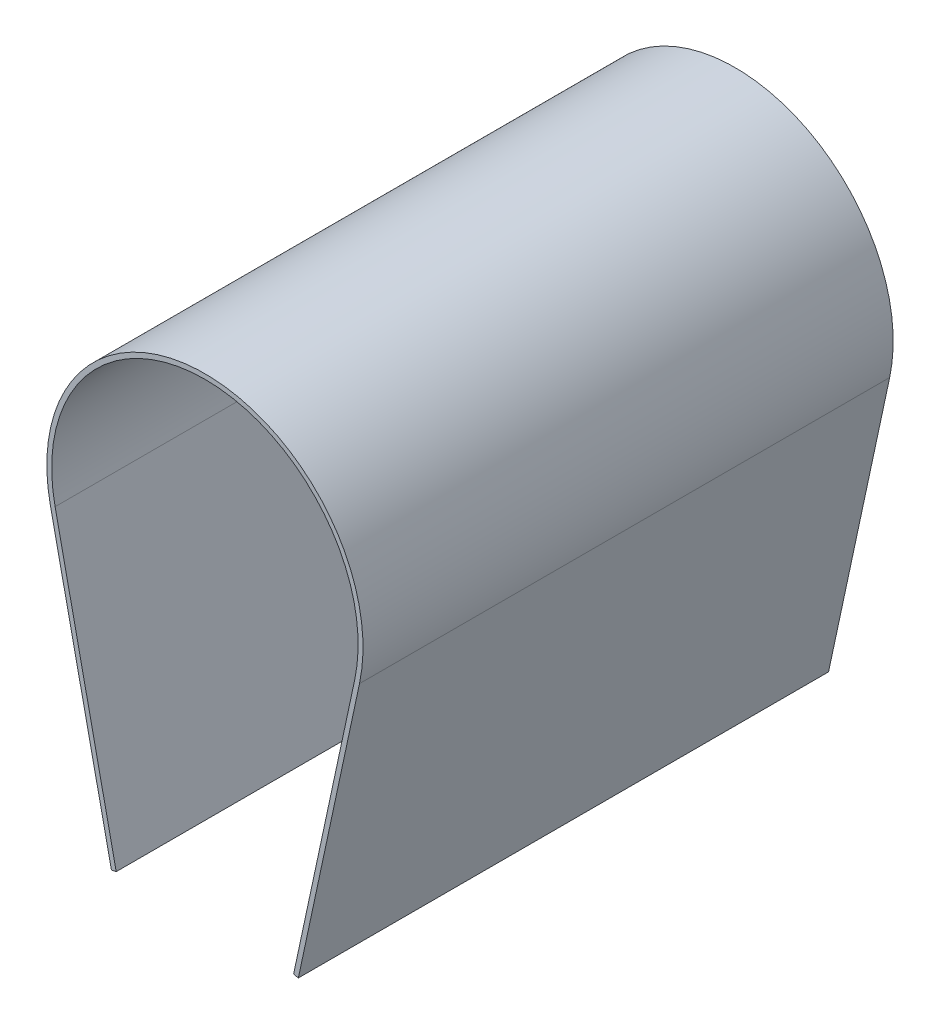
SolidWorks part; units mm, degrees
ref_plane "Front Plane" through (0, 0, 0) normal (0, 0, 1) x (1, 0, 0)
ref_plane "Top Plane" through (0, 0, 0) normal (0, 1, 0) x (1, 0, 0)
ref_plane "Right Plane" through (0, 0, 0) normal (1, 0, 0) x (0, 0, -1)
sketch "Cross Section Sketch" plane through (0, 0, 0) normal (0, 0, 1) x (1, 0, 0)
  line L0 (-290, -1750) -> (290, -1750) construction
  line L1 (0, 0) -> (0, -1750) construction
  line L2 (-384.2192, -1310) -> (-364.6625, -1305.8122)
  line L3 (635.5913, -136.102) -> (384.2192, -1310)
  line L4 (384.2192, -1310) -> (290, -1750) construction
  line L5 (384.2192, -1310) -> (364.6625, -1305.8122)
  line L6 (364.6625, -1305.8122) -> (616.0346, -131.9143)
  line L7 (-364.6625, -1305.8122) -> (-616.0346, -131.9143)
  line L8 (-635.5913, -136.102) -> (-384.2192, -1310)
  line L9 (384.2192, -1310) -> (0, -1310) construction
  arc A0 (635.5913, -136.102) -> (-635.5913, -136.102) centre (0, 0) ccw
  arc A1 (616.0346, -131.9143) -> (-616.0346, -131.9143) centre (0, 0) ccw
  point P6 (0, -1750)
  dimension "D1" = 1300
  dimension "D2" = 20
  dimension "D3" = 20
  dimension "D4" = 1310
  dimension "D5" = 1750
  dimension "D6" = 580
extrude "Cross Section Extrude" add sketch "Cross Section Sketch" along normal blind 2180
